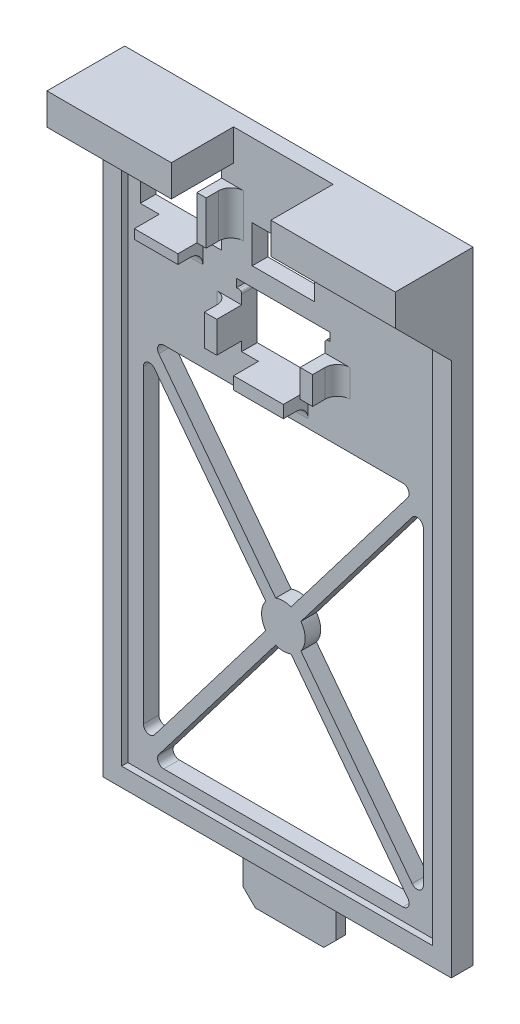
SolidWorks part; units mm, degrees
material "PE Low/Medium Density"
ref_plane "Front Plane" through (0, 0, 0) normal (0, 0, 1) x (1, 0, 0)
ref_plane "Top Plane" through (0, 0, 0) normal (0, 1, 0) x (1, 0, 0)
ref_plane "Right Plane" through (0, 0, 0) normal (1, 0, 0) x (0, 0, -1)
sketch "Sketch1" plane through (0, 0, 0) normal (0, 0, 1) x (1, 0, 0)
  line L0 (28, -2.9) -> (28, -9.4) construction
  line L1 (-28, -6.95) -> (28, -6.95)
  line L2 (-28, -6.95) -> (-28, -106.95)
  line L3 (-28, -106.95) -> (28, -106.95)
  line L4 (28, -6.95) -> (28, -106.95)
  dimension "D1" = 100
extrude "Boss-Extrude1" add sketch "Sketch1" along normal blind 2.5 contours L4 L3 L2 L1
sketch "Sketch2" plane through (0, 0, 2.5) normal (0, 0, 1) x (1, 0, 0)
  line L0 (-10, -12) -> (-23, -12) construction
  line L1 (-28, -6.95) -> (-8, -6.95)
  line L2 (-28, -6.95) -> (-28, -12)
  line L3 (-28, -12) -> (-8, -12)
  line L4 (-8, -6.95) -> (-8, -12)
  line L5 (28, -6.95) -> (8, -6.95)
  line L6 (28, -6.95) -> (28, -12)
  line L7 (28, -12) -> (8, -12)
  line L8 (8, -6.95) -> (8, -12)
  dimension "D1" = 20
extrude "Boss-Extrude2" add sketch "Sketch2" along normal blind 10
sketch "Sketch3" plane through (0, 0, 2.5) normal (0, 0, 1) x (1, 0, 0)
  line L0 (-28, -12) -> (-8, -12) construction
  line L1 (-9.9, -12) -> (-23, -12)
  line L2 (-9.9, -12) -> (-9.9, -25.1)
  line L3 (-9.9, -25.1) -> (-23, -25.1)
  line L4 (-23, -12) -> (-23, -25.1)
  line L6 (-23, -25) -> (-23, -12) construction
  dimension "D1" = 13.1
  dimension "D2" = 13.1
extrude "Cut-Extrude1" cut sketch "Sketch3" against normal through all
sketch "Sketch4" plane through (28, 0, 0) normal (1, 0, 0) x (0, 0, -1)
  line L0 (-12.5, -12) -> (-2.5, -12)
  line L1 (-2.5, -12) -> (-2.5, -22)
  line L2 (-2.5, -12) -> (-2.5, -106.95) construction
  line L3 (-2.5, -22) -> (-12.5, -12)
  dimension "D1" = 45
extrude "Boss-Extrude3" add sketch "Sketch4" against normal blind 5
sketch "Sketch5" plane through (-28, 0, 0) normal (-1, 0, 0) x (0, 0, 1)
  line L4 (2.5, -22) -> (12.5, -12)
  line L5 (12.5, -12) -> (2.5, -12)
  line L6 (2.5, -12) -> (2.5, -22)
  line L7 (2.5, -22) -> (12.5, -12)
  line L8 (12.5, -12) -> (2.5, -12)
  line L9 (2.5, -12) -> (2.5, -22)
  dimension "D1" = 0
extrude "Boss-Extrude4" add sketch "Sketch5" against normal blind 5
sketch "Sketch6" plane through (0, 0, 2.5) normal (0, 0, 1) x (1, 0, 0)
  line L0 (-23, -25.1) -> (-9.9, -25.1) construction
  line L1 (-12.95, -25.1) -> (-19.95, -25.1)
  line L2 (-12.95, -25.1) -> (-12.95, -26.6)
  line L3 (-12.95, -26.6) -> (-19.95, -26.6)
  line L4 (-19.95, -25.1) -> (-19.95, -26.6)
  line L5 (-9.9, -25.1) -> (-9.9, -12) construction
  line L6 (-9.9, -22.05) -> (-8.4, -22.05)
  line L7 (-9.9, -22.05) -> (-9.9, -15.05)
  line L8 (-9.9, -15.05) -> (-8.4, -15.05)
  line L9 (-8.4, -22.05) -> (-8.4, -15.05)
  line L10 (-16.45, -25.1) -> (-16.45, -26.6) construction
  line L11 (-8.4, -18.55) -> (-9.9, -18.55) construction
  dimension "D1" = 1.5
  dimension "D2" = 7
extrude "Boss-Extrude5" add sketch "Sketch6" along normal blind 4
sketch "Sketch7" plane through (0, 0, 2.5) normal (0, 0, 1) x (1, 0, 0)
  line L1 (7.5, -29.1) -> (-7.5, -29.1)
  line L2 (7.5, -29.1) -> (7.5, -27.8)
  line L3 (7.5, -27.8) -> (-7.5, -27.8)
  line L4 (-7.5, -29.1) -> (-7.5, -27.8)
extrude "Cut-Extrude2" cut sketch "Sketch7" against normal through all
sketch "Sketch8" plane through (0, 0, 2.5) normal (0, 0, 1) x (1, 0, 0)
  line L0 (-7.5, -29.1) -> (7.5, -29.1) construction
  line L1 (6.7, -29.1) -> (-6.7, -29.1)
  line L2 (6.7, -29.1) -> (6.7, -37.6)
  line L3 (6.7, -37.6) -> (-6.7, -37.6)
  line L4 (-6.7, -29.1) -> (-6.7, -37.6)
  line L5 (0, -37.6) -> (0, -27.8) construction
  line L6 (7.5, -27.8) -> (-7.5, -27.8) construction
  line L7 (0, -24.8) -> (0, -37.6) construction
  line L8 (5, -24.8) -> (-5, -24.8)
  line L9 (5, -24.8) -> (5, -18.8)
  line L10 (5, -18.8) -> (-5, -18.8)
  line L11 (-5, -24.8) -> (-5, -18.8)
  dimension "D1" = 13.4
  dimension "D2" = 8.5
  dimension "D3" = 10
  dimension "D4" = 6
  dimension "D5" = 3
extrude "Cut-Extrude3" cut sketch "Sketch8" against normal through all
fillet "Fillet1" radius 2 2 edges at (-16.45, -26.6, 2.5) (-8.4, -18.55, 2.5)
sketch "Sketch9" plane through (0, 0, 2.5) normal (0, 0, 1) x (1, 0, 0)
  line L0 (-28, -106.95) -> (28, -106.95) construction
  line L1 (7.5, -106.95) -> (-7.5, -106.95)
  line L2 (7.5, -106.95) -> (7.5, -114.95)
  line L3 (7.5, -114.95) -> (-7.5, -114.95)
  line L4 (-7.5, -106.95) -> (-7.5, -114.95)
  line L5 (0, -114.95) -> (0, -37.6) construction
  line L6 (-6.7, -37.6) -> (6.7, -37.6) construction
  dimension "D1" = 8
  dimension "D2" = 15
extrude "Boss-Extrude6" add sketch "Sketch9" against normal up to surface (2.5 mm away) contours L3 L4 L1 L2 up to face at (0, -21.8, 0)
chamfer "Chamfer1" distance 2 angle 45 2 edges at (7.5, -114.95, 1.25) (-7.5, -114.95, 1.25)
sketch "Sketch10" plane through (0, 0, 2.5) normal (0, 0, 1) x (1, 0, 0)
  line L0 (0, -114.95) -> (0, -101.95) construction
  line L1 (22.5, -101.95) -> (-22.5, -101.95)
  line L2 (22.5, -101.95) -> (22.5, -42.95)
  line L3 (22.5, -42.95) -> (-22.5, -42.95)
  line L4 (-22.5, -101.95) -> (-22.5, -42.95)
  line L5 (5.5, -114.95) -> (-5.5, -114.95) construction
  dimension "D1" = 13
  dimension "D2" = 59
  dimension "D3" = 45
extrude "Cut-Extrude4" cut sketch "Sketch10" against normal blind 4 contours L3 L4 L1 L2
sketch "Sketch11" plane through (0, 0, 2.5) normal (0, 0, 1) x (1, 0, 0)
  line L0 (-22.5, -42.95) -> (22.5, -101.95) construction
  line L1 (-22.5, -101.95) -> (22.5, -42.95) construction
  line L2 (-22.5, -42.95) -> (-21.2423, -42.95)
  line L3 (22.5, -42.95) -> (-22.5, -42.95) construction
  line L4 (-21.2423, -42.95) -> (22.5, -100.3011)
  line L5 (22.5, -101.95) -> (22.5, -42.95) construction
  line L6 (22.5, -100.3011) -> (22.5, -101.95)
  line L7 (22.5, -101.95) -> (21.2423, -101.95)
  line L8 (21.2423, -101.95) -> (-22.5, -44.5989)
  line L9 (-22.5, -101.95) -> (-22.5, -42.95) construction
  line L10 (-22.5, -44.5989) -> (-22.5, -42.95)
  line L11 (22.5, -42.95) -> (21.2423, -42.95)
  line L12 (21.2423, -42.95) -> (-22.5, -100.3011)
  line L13 (-22.5, -100.3011) -> (-22.5, -101.95)
  line L14 (-22.5, -101.95) -> (-21.2423, -101.95)
  line L15 (22.5, -101.95) -> (-22.5, -101.95) construction
  line L16 (-21.2423, -101.95) -> (22.5, -44.5989)
  line L17 (22.5, -44.5989) -> (22.5, -42.95)
  circle A0 centre (0, -72.45) radius 3.5
  line M9 (-22.5, -42.95) -> (22.5, -42.95)
  line M10 (22.5, -42.95) -> (22.5, -101.95)
  line M11 (22.5, -101.95) -> (-22.5, -101.95)
  line M12 (-22.5, -101.95) -> (-22.5, -42.95)
  dimension "D3" = 7
  dimension "D1" = 2
  dimension "D2" = 2
extrude "Boss-Extrude7" add sketch "Sketch11" against normal up to surface (2.5 mm away) contours A0 L4 L8 M9 M12 | A0 L16 L12 M10 M9 | A0 L8 L4 M11 M10 | A0 L12 L16 M12 M11 | L8 A0 L12 | L4 A0 L8 L12 | L12 A0 L16 L8 | L16 A0 L8 | L4 A0 L16 | L8 A0 L4 L16 | L16 A0 L12 L4 | L12 A0 L4 | L8 L16 L4 L12 region at (-12.1383, -56.5308, 2.5) region at (0, -69.6184, 2.5) region at (-1.3883, -70.6922, 2.5) region at (12.1383, -56.5308, 2.5) region at (-2.5973, -72.45, 2.5) region at (-12.1383, -88.3692, 2.5) region at (1.3883, -70.6922, 2.5) region at (0, -72.45, 2.5) region at (-1.3883, -74.2078, 2.5) region at (2.5973, -72.45, 2.5) region at (1.3883, -74.2078, 2.5) region at (0, -75.2816, 2.5) region at (12.1383, -88.3692, 2.5) up to face at (0, -72.45, 0)
fillet "Fillet2" radius 1 8 edges at (-22.5, -100.3011, 1.25) (-21.2423, -101.95, 1.25) (-22.5, -44.5989, 1.25) (-21.2423, -42.95, 1.25) (22.5, -44.5989, 1.25) (21.2423, -42.95, 1.25) (22.5, -100.3011, 1.25) (21.2423, -101.95, 1.25)
fillet "Fillet3" radius 0.5 2 edges at (-6.7, -29.1, 1.25) (6.7, -29.1, 1.25)
sketch "Sketch12" plane through (0, 0, 2.5) normal (0, 0, 1) x (1, 0, 0)
  line L0 (-7.5, -106.95) -> (7.5, -106.95)
  line L1 (7.5, -106.95) -> (7.5, -112.95)
  line L2 (7.5, -112.95) -> (5.5, -114.95)
  line L3 (5.5, -114.95) -> (-5.5, -114.95)
  line L4 (-5.5, -114.95) -> (-7.5, -112.95)
  line L5 (-7.5, -112.95) -> (-7.5, -106.95)
extrude "Cut-Extrude5" cut sketch "Sketch12" against normal blind 1
sketch "Sketch13" plane through (28, 0, 0) normal (1, 0, 0) x (0, 0, -1)
  line L0 (-2.5, -106.95) -> (-3.5, -106.95)
  line L1 (-3.5, -106.95) -> (-3.5, -18.95)
  line L2 (-3.5, -18.95) -> (-2.5, -18.95)
  line L3 (-2.5, -18.95) -> (-2.5, -106.95)
  dimension "D1" = 1
  dimension "D2" = 88
extrude "Boss-Extrude8" add sketch "Sketch13" against normal blind 3
sketch "Sketch14" plane through (-28, 0, 0) normal (-1, 0, 0) x (0, 0, 1)
  line L0 (3.5, -21) -> (3.5, -106.95) construction
  line L1 (3.5, -21) -> (3.5, -106.95)
  line L2 (2.5, -22) -> (2.5, -106.95) construction
  line L3 (2.5, -22) -> (2.5, -106.95)
  line L4 (2.5, -22) -> (3.5, -21)
  line L5 (2.5, -106.95) -> (3.5, -106.95)
extrude "Boss-Extrude9" add sketch "Sketch14" against normal blind 3
sketch "Sketch15" plane through (0, 0, 2.5) normal (0, 0, 1) x (1, 0, 0)
  line L0 (25, -106.95) -> (25, -22) construction
  line L1 (-25, -106.95) -> (25, -106.95)
  line L2 (-25, -106.95) -> (-25, -103.95)
  line L3 (-25, -103.95) -> (25, -103.95)
  line L4 (25, -106.95) -> (25, -103.95)
  dimension "D1" = 3
extrude "Boss-Extrude10" add sketch "Sketch15" along normal up to surface (1 mm away) up to face at (-26.5, -63.975, 3.5)
sketch "Sketch16" plane through (0, 0, 2.5) normal (0, 0, 1) x (1, 0, 0)
  line L0 (-6.7, -29.6) -> (-6.7, -37.6) construction
  line L1 (-6.7, -31.1) -> (-8.7, -31.1)
  line L2 (-6.7, -31.1) -> (-6.7, -36.1)
  line L3 (-6.7, -36.1) -> (-8.7, -36.1)
  line L4 (-8.7, -31.1) -> (-8.7, -36.1)
  line L5 (-6.7, -37.6) -> (6.7, -37.6) construction
  line L6 (-4, -37.6) -> (4, -37.6)
  line L7 (-4, -37.6) -> (-4, -39.6)
  line L8 (-4, -39.6) -> (4, -39.6)
  line L9 (4, -37.6) -> (4, -39.6)
  line L10 (6.7, -37.6) -> (6.7, -29.6) construction
  line L11 (6.7, -35.5347) -> (8.7, -35.5347)
  line L12 (6.7, -35.5347) -> (6.7, -31.1)
  line L13 (6.7, -31.1) -> (8.7, -31.1)
  line L14 (8.7, -35.5347) -> (8.7, -31.1)
  line L15 (-6.7, -31.1) -> (6.7, -31.1) construction
  line L16 (0, -37.6) -> (0, -39.6) construction
  point P20 (0, -37.6)
  dimension "D1" = 8
  dimension "D2" = 2
  dimension "D3" = 2
  dimension "D4" = 5
  dimension "D5" = 1.5
extrude "Boss-Extrude11" add sketch "Sketch16" along normal blind 4
fillet "Fillet4" radius 2 3 edges at (-8.7, -33.6, 2.5) (0, -39.6, 2.5) (8.7, -33.3173, 2.5)
